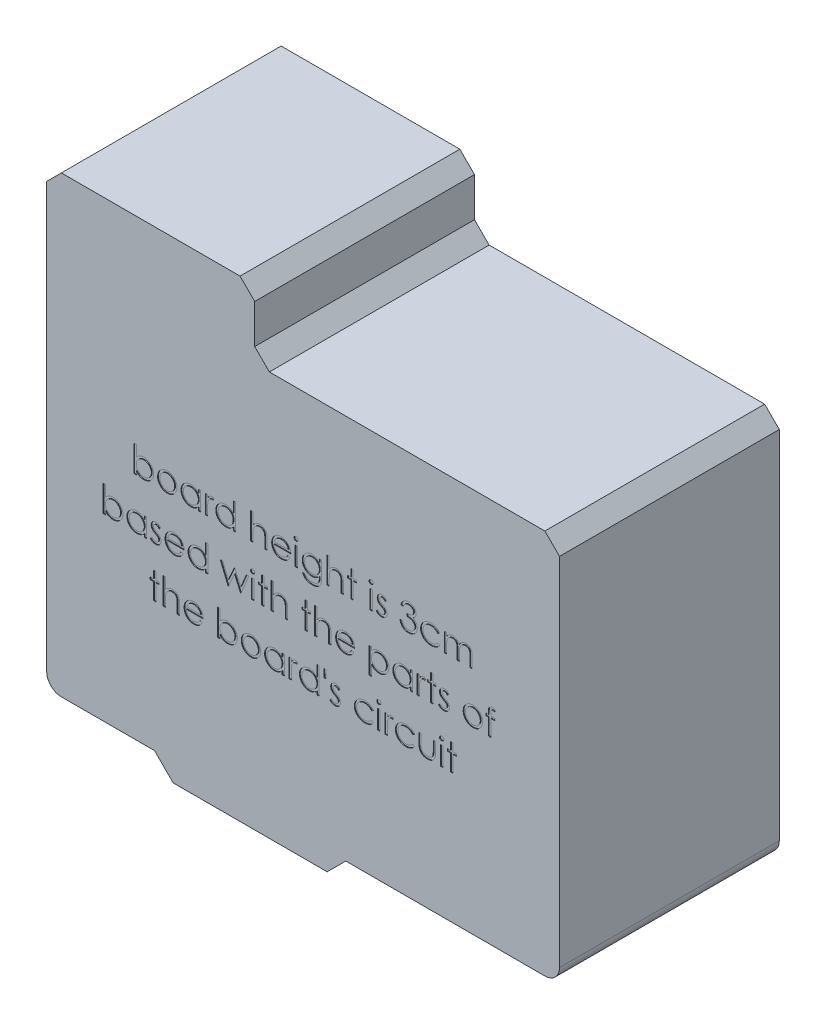
SolidWorks part; units mm, degrees
ref_plane "정면" through (0, 0, 0) normal (0, 0, 1) x (1, 0, 0)
ref_plane "윗면" through (0, 0, 0) normal (0, 1, 0) x (1, 0, 0)
ref_plane "우측면" through (0, 0, 0) normal (1, 0, 0) x (0, 0, -1)
sketch "스케치1" plane through (0, 0, 0) normal (0, 0, 1) x (1, 0, 0)
  line L1 (-35, 32.238) -> (35, 32.238)
  line L2 (-35, 32.238) -> (-35, -32.238)
  line L3 (-35, -32.238) -> (35, -32.238)
  line L4 (35, 32.238) -> (35, -32.238)
  line L5 (-35, 32.238) -> (35, -32.238) construction
  line L6 (-35, -32.238) -> (35, 32.238) construction
  point P0 (0, 0)
  dimension "D1" = 70
  dimension "D2" = 64.476
extrude "보스-돌출1" add sketch "스케치1" along normal blind 30
sketch "스케치2" plane through (0, 0, 30) normal (0, 0, 1) x (1, 0, 0)
  line L0 (-35, 30.238) -> (-35, 32.238)
  line L1 (-35, 32.238) -> (-35, -32.238) construction
  line L2 (-35, 32.238) -> (-33, 32.238)
  line L3 (35, 32.238) -> (-35, 32.238) construction
  line L4 (-33, 32.238) -> (-35, 30.238)
  dimension "D1" = 2
  dimension "D2" = 2
extrude "컷-돌출1" cut sketch "스케치2" against normal blind 30
sketch "스케치3" plane through (0, 0, 30) normal (0, 0, 1) x (1, 0, 0)
  line L0 (-8.604, 32.238) -> (-6.604, 30.238)
  line L1 (35, 32.238) -> (-33, 32.238) construction
  line L2 (-6.604, 30.238) -> (-6.604, 24.9057)
  line L3 (-6.604, 24.9057) -> (-4.604, 22.9057)
  line L4 (-4.604, 22.9057) -> (33, 22.9057)
  line L5 (33, 22.9057) -> (35, 20.9057)
  line L6 (35, -32.238) -> (35, 32.238) construction
  line L7 (35, 20.9057) -> (35, 32.238)
  line L8 (35, 32.238) -> (-8.604, 32.238)
  point P4 (-9.9593, 32.238)
  point P13 (0, 0)
  point P15 (30.5144, 22.4875)
  dimension "D1" = 28.396
  dimension "D2" = 135
  dimension "D3" = 0
  dimension "D4" = 135
  dimension "D5" = 2
  dimension "D6" = 2
extrude "컷-돌출2" cut sketch "스케치3" against normal blind 30
sketch "스케치4" plane through (0, 0, 30) normal (0, 0, 1) x (1, 0, 0)
  line L1 (35, -32.238) -> (35, 20.9057) construction
  line L2 (35, -27.698) -> (35, -32.238)
  line L3 (35, -32.238) -> (3.2847, -32.238)
  line L5 (-35, -32.238) -> (35, -32.238) construction
  line L6 (3.2847, -32.238) -> (5.8247, -29.698)
  line L7 (5.8247, -29.698) -> (33, -29.698)
  line L12 (-17.7354, -32.238) -> (-20.2754, -29.698)
  line L13 (-20.2754, -29.698) -> (-33, -29.698)
  line L14 (-17.7354, -32.238) -> (-35, -32.238)
  line L15 (-35, -32.238) -> (-35, -27.698)
  line L16 (-35, 30.238) -> (-35, -32.238) construction
  arc A0 (33, -29.698) -> (35, -27.698) centre (33, -27.698) ccw
  arc A2 (-35, -27.698) -> (-33, -29.698) centre (-33, -27.698) ccw
  point P13 (-35, -27.698)
  point P21 (-32.7848, -27.0376)
  dimension "D1" = 2
  dimension "D4" = 2
  dimension "D2" = 45
  dimension "D3" = 2.54
  dimension "D5" = 2.54
  dimension "D6" = 4.54
  dimension "D7" = 4.54
  dimension "D8" = 45
extrude "컷-돌출3" cut sketch "스케치4" against normal blind 30
sketch "스케치5" plane through (0, 0, 30) normal (0, 0, 1) x (1, 0, 0)
  line L0 (-35, 1.6499) -> (35, 1.6499) construction
  line L1 (-35, 30.238) -> (-35, -27.698) construction
  line L2 (35, -27.698) -> (35, 20.9057) construction
  text T0 "board height is 3cm\r\nbased with the parts of \r\nthe board's circuit\r\n"
extrude "컷-돌출4" cut sketch "스케치5" against normal blind 0.1
